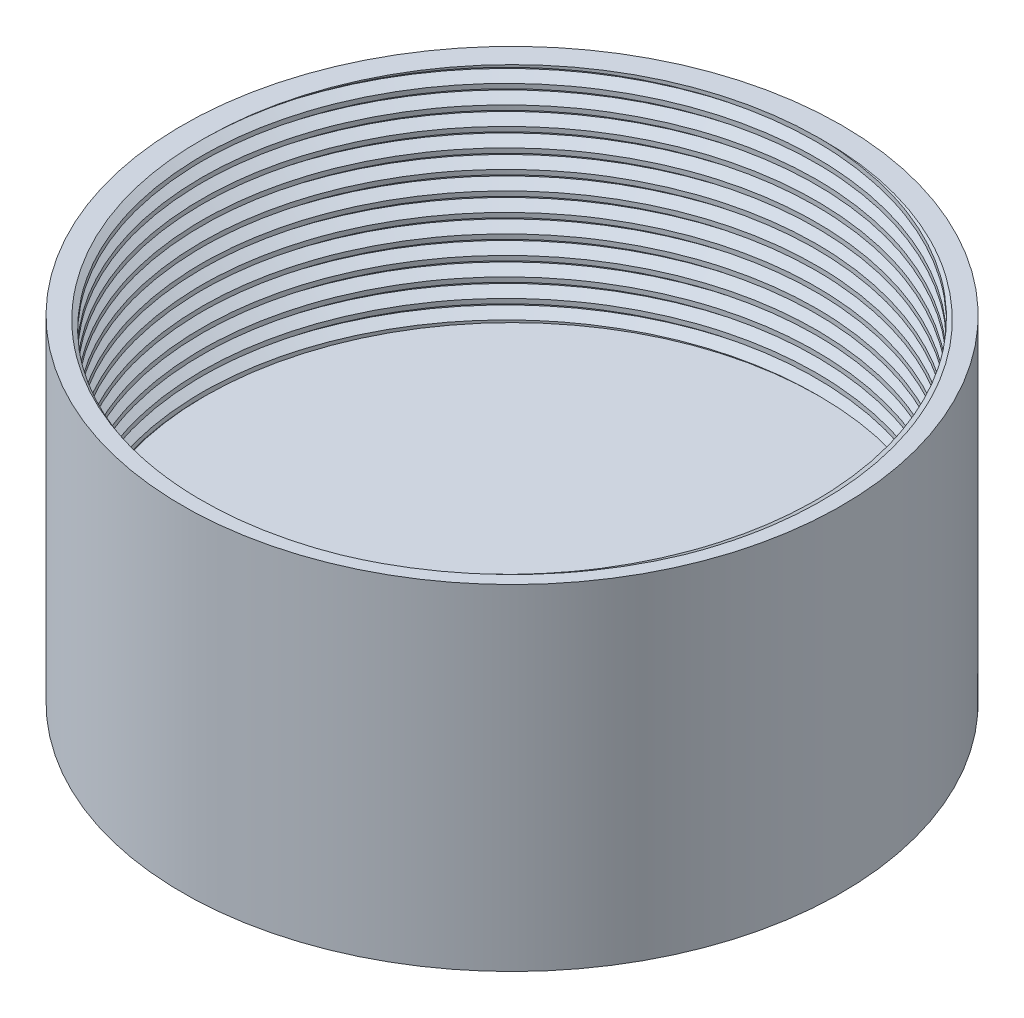
SolidWorks part; units mm, degrees
ref_plane "Front Plane" through (0, 0, 0) normal (0, 0, 1) x (1, 0, 0)
ref_plane "Top Plane" through (0, 0, 0) normal (0, 1, 0) x (1, 0, 0)
ref_plane "Right Plane" through (0, 0, 0) normal (1, 0, 0) x (0, 0, -1)
sketch "Sketch1" plane through (0, 0, 0) normal (0, 1, 0) x (1, 0, 0)
  circle A0 centre (0, 0) radius 37.465
  dimension "D1" = 74.93
extrude "Boss-Extrude1" add sketch "Sketch1" along normal blind 38.1 contours A0
sketch "Sketch2" plane through (0, 38.1, 0) normal (0, 1, 0) x (1, 0, 0)
  circle A0 centre (0, 0) radius 34.925
  dimension "D1" = 69.85
extrude "Cut-Extrude1" cut sketch "Sketch2" against normal blind 25.4
thread "Thread1" pitch 2.1167 method cut profile "Thread Profile1" start angle 0, offset 6.35, length 35.4, pitch 2.1167, diameter 69.85
ref_plane "Plane1" through (-34.925, 44.45, 0) normal (0, 0, 1) x (-1, 0, 0)
sketch "Thread Profile1" plane through (-34.925, 44.45, 0) normal (0, 0, 1) x (-1, 0, 0)
  line L0 (0, 0) -> (0, 2.1167) construction
  line L1 (0, 0) -> (1.1457, 0.6615)
  line L2 (1.1457, 0.6615) -> (1.1457, 0.926)
  line L3 (1.1457, 0.926) -> (0, 1.5875)
  line L4 (1.1457, 0.7937) -> (0, 0.7937) construction
  line L11 (0, 0) -> (0, 1.5875)
  point P2 (0, 0)
  dimension "Pitch" = 2.1167
  dimension "Profile_Angle" = 60
  dimension "Profile_Land" = 0.2646
  dimension "Profile_Height" = 1.1457
